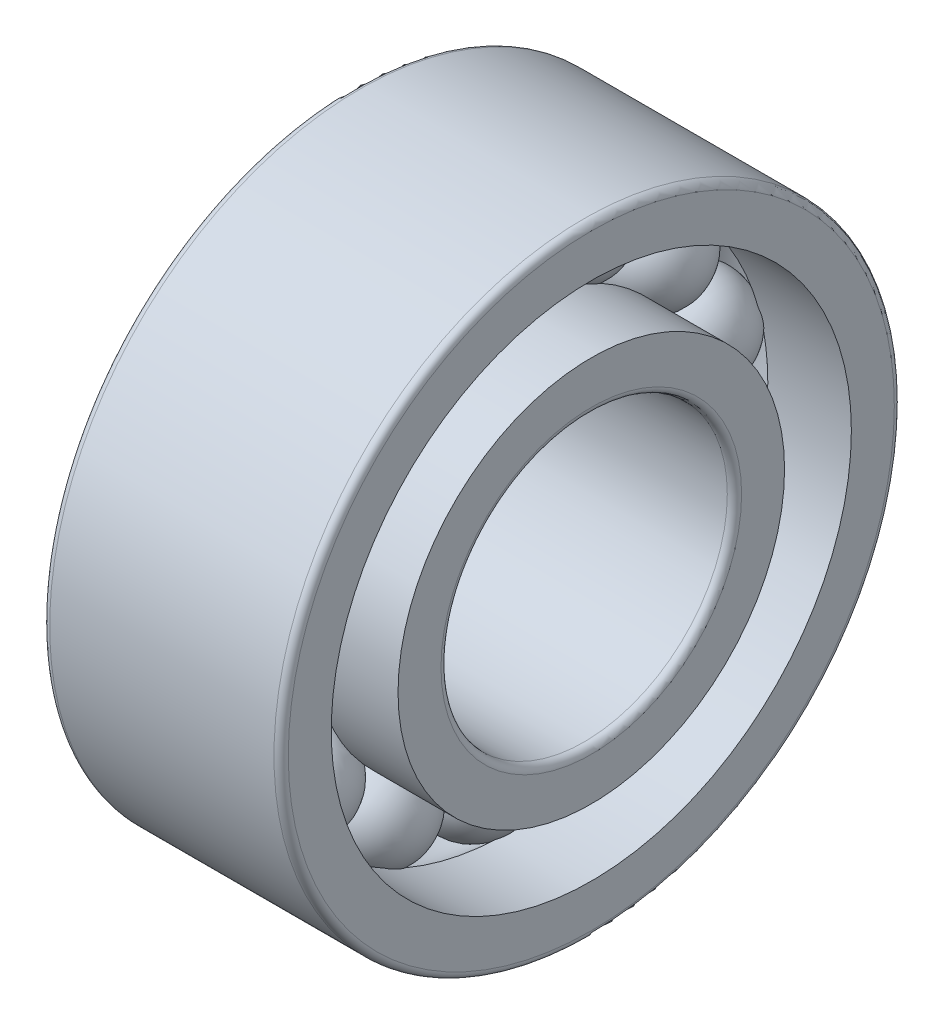
SolidWorks part; units mm, degrees
ref_plane "Plane1" through (0, 0, 0) normal (0, 0, 1) x (1, 0, 0)
ref_plane "Plane2" through (0, 0, 0) normal (0, 1, 0) x (1, 0, 0)
ref_plane "Plane3" through (0, 0, 0) normal (1, 0, 0) x (0, 0, -1)
other "Configuration Table"
sketch "Clipboard" plane through (0, 0, 0) normal (0, 0, 1) x (1, 0, 0)
  line L0 (-10, 0) -> (10, 0) construction
  line L1 (0, 0) -> (21.6965, -5.4095)
  line L2 (0, 0) -> (4.7493, -0.0829)
  line L3 (0, 0) -> (22.3573, 0.3902)
  line L4 (0, 0) -> (-22.3573, -0.3902)
  dimension "BallCLRad" = 4.75
sketch "CagSpiSke" plane through (0, 0, 0) normal (0, 0, 1) x (1, 0, 0)
  line L0 (0.105, 4.575) -> (0.105, 4.925)
  line L1 (0.105, 4.925) -> (-0.105, 4.925)
  line L2 (-0.105, 4.925) -> (-0.105, 4.575)
  line L3 (-0.105, 4.575) -> (0.105, 4.575)
  line L4 (-20.6375, 0) -> (20.6375, 0) construction
  line L5 (0, 0) -> (0, 23.7692) construction
  dimension "OD" = 9.85
  dimension "ID" = 9.15
revolve "CageSpine" add sketch "CagSpiSke" angle 0.001 about L4
ref_axis "Axis1" through (-50, 0, 0) along (1, 0, 0)
sketch "CagBalSke" plane through (0, 0, 0) normal (0, 0, 1) x (1, 0, 0)
  line L0 (-1.155, 4.75) -> (1.155, 4.75)
  line L1 (-1.905, 4.75) -> (1.905, 4.75) construction
  line L2 (-10, 0) -> (10, 0) construction
  line L3 (0, 0) -> (0, 24) construction
  arc A0 (1.155, 4.75) -> (-1.155, 4.75) centre (0, 4.75) cw
  dimension "BallCLRad" = 4.75
revolve "CageBall" [suppressed] add sketch "CagBalSke" angle 360 about L1 reverse direction yes
pattern_circular "CageBalls" [suppressed] count 14 every 25.714 about axis through (-50, 0, 0) along (1, 0, 0)
sketch "CagTrmODSke" plane through (0, 0, 0) normal (0, 0, 1) x (1, 0, 0)
  line L0 (1.156, 4.925) -> (1.156, 5.906)
  line L1 (1.156, 5.906) -> (-1.156, 5.906)
  line L2 (-1.156, 5.906) -> (-1.156, 4.925)
  line L3 (-1.156, 4.925) -> (1.156, 4.925)
  line L4 (-20.6375, 0) -> (20.6375, 0) construction
  line L5 (0, 0) -> (0, 25) construction
  dimension "Width" = 2.312
  dimension "ID" = 9.85
  dimension "OD" = 11.812
revolve "CageTrimOD" [suppressed] cut sketch "CagTrmODSke" angle 360 about L4 reverse direction yes
sketch "CagTrmIDSke" plane through (0, 0, 0) normal (0, 0, 1) x (1, 0, 0)
  line L0 (1.156, 3.596) -> (1.156, 4.575)
  line L1 (1.156, 4.575) -> (-1.156, 4.575)
  line L2 (-1.156, 4.575) -> (-1.156, 3.596)
  line L3 (-1.156, 3.596) -> (1.156, 3.596)
  line L4 (-20.6375, 0) -> (20.6375, 0) construction
  line L5 (0, 0) -> (0, 25) construction
  dimension "Width" = 2.312
  dimension "ID" = 7.192
  dimension "OD" = 9.15
revolve "CageTrimID" [suppressed] cut sketch "CagTrmIDSke" angle 360 about L4 reverse direction yes
sketch "BalSimSke" plane through (0, 0, 0) normal (0, 0, 1) x (1, 0, 0)
  line L0 (-10, 0) -> (10, 0) construction
  line L1 (-10, 4.75) -> (10, 4.75) construction
  line L2 (0, 0) -> (0, 23) construction
  circle A0 centre (0, 4.75) radius 1.05
  dimension "BallCLRad" = 4.75
  dimension "Ball_diameter" = 2.1
revolve "BallsSimplified" [suppressed] add sketch "BalSimSke" angle 360 about L0
sketch "BalDetSke" plane through (0, 0, 0) normal (0, 0, 1) x (1, 0, 0)
  line L0 (-1.05, 4.75) -> (1.05, 4.75)
  line L1 (-1.905, 4.75) -> (1.905, 4.75) construction
  line L2 (0, 0) -> (0, 25) construction
  arc A0 (1.05, 4.75) -> (-1.05, 4.75) centre (0, 4.75) cw
  dimension "BallCLRad" = 4.75
  dimension "Ball_diameter" = 2.1
revolve "BallDetailed" add sketch "BalDetSke" angle 360 about L1 reverse direction yes
sketch "InnRacSke" plane through (0, 0, 0) normal (0, 0, 1) x (1, 0, 0)
  line L0 (-0.7487, 4.05) -> (-2.5, 4.05)
  line L1 (-2.5, 4.05) -> (-2.5, 3.15)
  line L2 (-2.35, 3) -> (2.35, 3)
  line L3 (2.5, 3.15) -> (2.5, 4.05)
  line L4 (2.5, 4.05) -> (0.7487, 4.05)
  line L5 (-20.6375, 0) -> (20.6375, 0) construction
  line L6 (0, 0) -> (0, 30) construction
  arc A0 (-2.5, 3.15) -> (-2.35, 3) centre (-2.35, 3.15) ccw
  arc A1 (2.35, 3) -> (2.5, 3.15) centre (2.35, 3.15) ccw
  arc A2 (0.7487, 4.05) -> (-0.7487, 4.05) centre (0, 4.75) cw
  dimension "BallCLRad" = 4.75
  dimension "Fillet_radius" = 0.15
  dimension "Ball_diameter" = 2.05
  dimension "ID" = 6
  dimension "OD" = 8.1
  dimension "Width" = 5
revolve "InnerRace" add sketch "InnRacSke" angle 360 about L5 reverse direction yes
sketch "OutRacSke" plane through (0, 0, 0) normal (0, 0, 1) x (1, 0, 0)
  line L0 (-0.7487, 5.45) -> (-2.5, 5.45)
  line L1 (-2.5, 5.45) -> (-2.5, 6.35)
  line L2 (-2.35, 6.5) -> (2.35, 6.5)
  line L3 (2.5, 6.35) -> (2.5, 5.45)
  line L4 (2.5, 5.45) -> (0.7487, 5.45)
  line L5 (-20.6375, 0) -> (20.6375, 0) construction
  line L6 (0, 0) -> (0, 30) construction
  arc A0 (-2.5, 6.35) -> (-2.35, 6.5) centre (-2.35, 6.35) cw
  arc A1 (2.35, 6.5) -> (2.5, 6.35) centre (2.35, 6.35) cw
  arc A2 (0.7487, 5.45) -> (-0.7487, 5.45) centre (0, 4.75) ccw
  dimension "BallCLRad" = 4.75
  dimension "Fillet_radius" = 0.15
  dimension "Ball_diameter" = 2.05
  dimension "Width" = 5
revolve "OuterRace" add sketch "OutRacSke" angle 360 about L5 reverse direction yes
pattern_circular "BallsDetailed" count 14 every 25.714 about axis through (-50, 0, 0) along (1, 0, 0) of "BallDetailed"
equation "\"BallCLRad@Clipboard\" = ( \"OD@OutRacSke\" + \"ID@InnRacSke\" ) / 4"
equation "\"BallCLRad@BalSimSke\" = \"BallCLRad@Clipboard\""
equation "\"BallCLRad@BalDetSke\" = \"BallCLRad@Clipboard\""
equation "\"BallCLRad@InnRacSke\" = \"BallCLRad@Clipboard\""
equation "\"BallCLRad@OutRacSke\" = \"BallCLRad@Clipboard\""
equation "\"Ball_diameter@InnRacSke\" = \"Ball_diameter@BalDetSke\" - 0.05"
equation "\"Ball_diameter@OutRacSke\" = \"Ball_diameter@BalDetSke\" - 0.05"
equation "\"Ball_diameter@BalSimSke\" = \"Ball_diameter@BalDetSke\""
equation "\"Width@OutRacSke\" = \"Width@InnRacSke\""
equation "\"Fillet_radius@OutRacSke\" = \"Fillet_radius@InnRacSke\""
equation "\"Max_count@Clipboard\" = int( 3.14159265 / atn(( \"Ball_diameter@BalDetSke\" / 2) / sqr( \"BallCLRad@Clipboard\"  *  \"BallCLRad@Clipboard\" - ( \"Ball_diameter@BalDetSke\" / 2) *  ( \"Ball_diameter@BalDetSke\" / 2))))"
equation "\"Max_count@Clipboard\" = ((sgn( \"Max_count@Clipboard\" - \"Count@Clipboard\" )-1)*( \"Max_count@Clipboard\" - \"Count@Clipboard\" ))/-2+ \"Count@Clipboard\""
equation "\"Count@BallsDetailed\" = int( \"Show_count@Clipboard\" ) "
equation "\"Count@BallsDetailed\" = ((sgn( \"Count@BallsDetailed\" - \"Max_count@Clipboard\" )-1)*( \"Count@BallsDetailed\" - \"Max_count@Clipboard\" ))/-2+ \"Max_count@Clipboard\""
equation "\"Count@BallsDetailed\" = ((sgn( \"Count@BallsDetailed\" - \"Min_count@Clipboard\" )+1)*( \"Count@BallsDetailed\" - \"Min_count@Clipboard\"))/2 +\"Min_count@Clipboard\""
equation "\"Angle@BallsDetailed\" = 360.0 / \"Max_count@Clipboard\""
equation "\"BallCLRad@CagBalSke\" = \"BallCLRad@Clipboard\""
equation "\"Count@CageBalls\" = \"Count@BallsDetailed\""
equation "\"Angle@CageBalls\" = \"Angle@BallsDetailed\""
equation "\"Angle@CageSpine\" =  \"Angle@CageBalls\" * ( \"Count@CageBalls\" -1 + int( \"Count@CageBalls\" / \"Max_count@Clipboard\" ) )  + 0.001 -  int( \"Count@CageBalls\" / \"Max_count@Clipboard\" ) * 0.001"
equation "\"Angle@CageSpine\" =  \"Angle@CageSpine\" * int( \"Min_count@Clipboard\" / 2) + int(1 / \"Min_count@Clipboard\")  * 0.001"
equation "\"CageWallOD@CagBalSke\" =  \"Ball_diameter@BalDetSke\" * 1.1"
equation "\"Thickness@CagSpiSke\" =  \"Ball_diameter@BalDetSke\" * 0.1"
equation "\"OD@CagTrmODSke\" = \"BallCLRad@Clipboard\" * 2 + \"CageWallOD@CagBalSke\" + 0.002"
equation "\"ID@CagTrmODSke\" = \"BallCLRad@Clipboard\" * 2 + \"Ball_diameter@BalDetSke\" / 6"
equation "\"OD@CagTrmIDSke\" = \"BallCLRad@Clipboard\" * 2 - \"Ball_diameter@BalDetSke\" / 6"
equation "\"ID@CagTrmIDSke\" = \"BallCLRad@Clipboard\" * 2 - \"CageWallOD@CagBalSke\" + 0.002"
equation "\"OD@CagSpiSke\" = \"ID@CagTrmODSke\""
equation "\"ID@CagSpiSke\" = \"OD@CagTrmIDSke\""
equation "\"Width@CagTrmODSke\" = \"CageWallOD@CagBalSke\" + 0.002"
equation "\"Width@CagTrmIDSke\" = \"CageWallOD@CagBalSke\" + 0.002"
